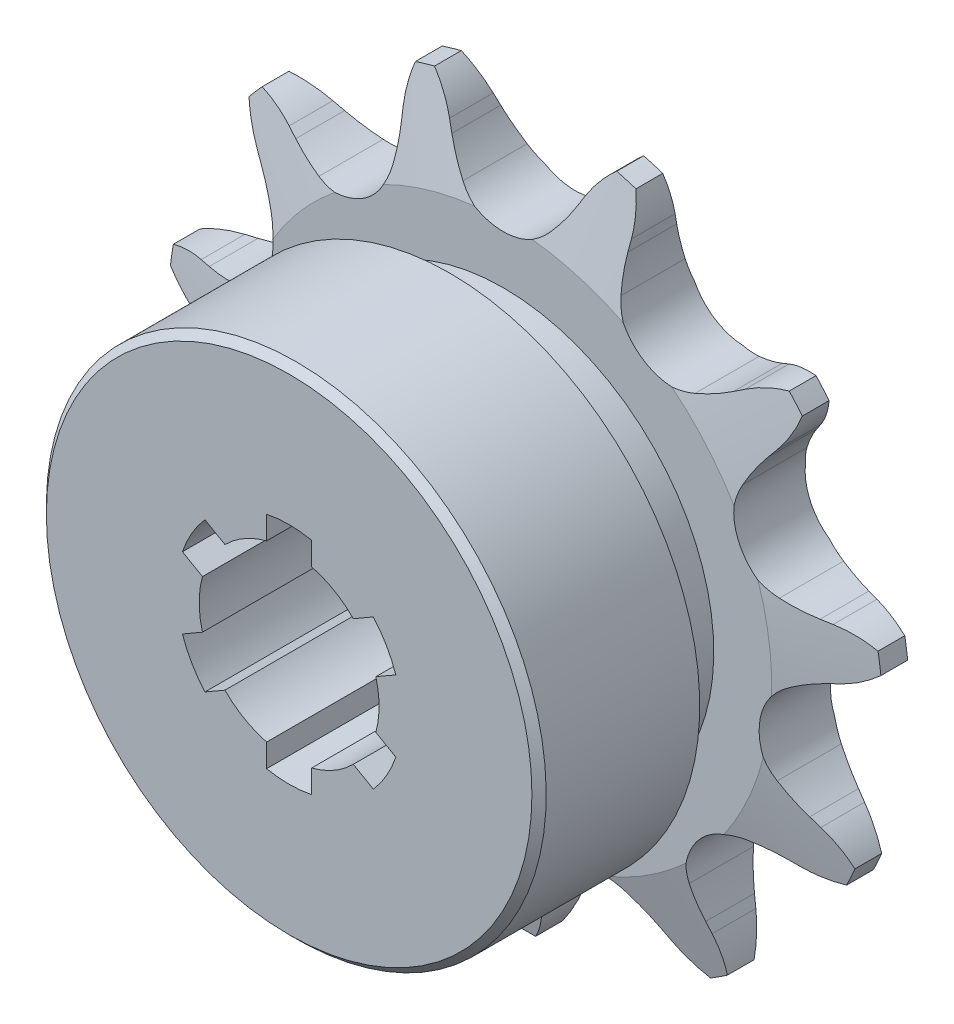
SolidWorks part; units mm, degrees
ref_plane "Front Plane" through (0, 0, 0) normal (0, 0, 1) x (1, 0, 0)
ref_plane "Top Plane" through (0, 0, 0) normal (0, 1, 0) x (1, 0, 0)
ref_plane "Right Plane" through (0, 0, 0) normal (1, 0, 0) x (0, 0, -1)
sketch "Sketch0" plane through (0, 0, 0) normal (0, 0, 1) x (1, 0, 0)
  line L0 (7.9375, -27.0326) -> (0, 0) construction
  line L1 (0, 0) -> (21.2924, -18.45) construction
  line L2 (0, 0) -> (-7.9375, -27.0326) construction
  line L3 (7.9375, -27.0326) -> (21.2924, -18.45) construction
  line L4 (7.9375, -27.0326) -> (-7.9375, -27.0326) construction
  line L5 (13.7041, -25.3103) -> (13.0504, -24.6313)
  line L6 (7.9375, -27.0326) -> (0, -29.3633) construction
  line L7 (2.1552, -28.7014) -> (2.338, -27.7767)
  line L8 (0, -27.0326) -> (0, -31.7951) construction
  line L9 (10.7525, -22.7279) -> (3.4891, -33.8353) construction
  line L10 (0, 0) -> (0, -27.0326) construction
  line L11 (13.0504, -24.6313) -> (3.4891, -33.8353) construction
  line L12 (0, -31.7951) -> (0, -32.9086) construction
  line L13 (19.9035, -19.3426) -> (13.7041, -25.3103) construction
  circle A0 centre (0, 0) radius 31.7951 construction
  circle A1 centre (0, 0) radius 28.1739 construction
  arc A2 (-8.2356, -35.414) -> (26.0745, -25.3397) centre (0, 0) ccw
  circle A3 centre (0, 0) radius 32.9086 construction
  circle A4 centre (7.9375, -27.0326) radius 5.08 construction
  arc A7 (10.7525, -22.7279) -> (3.242, -24.9331) centre (7.9375, -27.0326) ccw
  circle A8 centre (7.9375, -27.0326) radius 5.1435 construction
  arc A9 (13.7041, -25.3103) -> (26.0745, -25.3397) centre (19.9035, -19.3426) ccw
  arc A10 (13.0504, -24.6313) -> (10.7525, -22.7279) centre (3.4891, -33.8353) ccw
  arc A11 (2.1552, -28.7014) -> (-8.2356, -35.414) centre (-6.2865, -27.0326) cw
  arc A12 (2.338, -27.7767) -> (3.242, -24.9331) centre (15.3575, -30.3504) cw
  dimension "D1" = 5.1435
  dimension "R" = 5.1435
sketch "Sketch1" plane through (0, 0, 0) normal (1, 0, 0) x (0, 0, -1)
  line L0 (3.175, 0) -> (-3.175, 0)
  line L1 (-3.175, 0) -> (-3.175, 23.8576)
  line L2 (-3.175, 23.8576) -> (-1.1906, 31.7951)
  line L3 (-1.1906, 31.7951) -> (1.1906, 31.7951)
  line L4 (1.1906, 31.7951) -> (3.175, 23.8576)
  line L5 (3.175, 23.8576) -> (3.175, 0)
  line L7 (0, 31.7951) -> (0, 0) construction
  line L8 (-3.175, 23.8576) -> (3.175, 23.8576) construction
  line L9 (0, 31.7951) -> (0, -31.7951) construction
  line L10 (-3.175, 23.8576) -> (-3.175, 31.7951) construction
  line L11 (-3.175, 31.7951) -> (-1.1906, 31.7951) construction
  line L12 (1.1906, 31.7951) -> (3.175, 31.7951) construction
  line L13 (3.175, 31.7951) -> (3.175, 23.8576) construction
  line L14 (0, 0) -> (-6.4008, 0) construction
  line L22 (3.175, 0) -> (-22.225, 0) construction
  line L24 (-3.175, 0) -> (-3.175, 18.7141) construction
revolve "Revolve1" add sketch "Sketch1" angle 360 mid plane about L0
extrude "Cut-Extrude1" cut sketch "Sketch0" against normal through all and the other way through all
pattern_circular "CirPattern1" count 11 over 360 about axis through (0, 0, -3.175) along (0, 0, -1) of "Cut-Extrude1"
sketch "Sketch2" plane through (0, 0, 0) normal (0, 0, 1) x (1, 0, 0)
  circle A0 centre (0, 0) radius 7.9375 construction
  circle A1 centre (0, 0) radius 22.225
  circle A2 centre (0, 0) radius 31.75 construction
  dimension "Bore" = 15.875
  dimension "Hub Dia." = 44.45
  dimension "OD" = 63.5
extrude "Boss-Extrude1" add sketch "Sketch2" along normal up to vertex (22.225 mm away) from surface up to point (0, 0, 22.225) starting at face at (0, 0, 3.175)
sketch "Sketch3" plane through (0, 0, 0) normal (0, 0, 1) x (1, 0, 0)
  circle A0 centre (0, 0) radius 7.9375 construction
  circle A1 centre (0, 0) radius 7.9375
extrude "Cut-Extrude2" cut sketch "Sketch3" along normal through all and the other way through all
sketch "Sketch4" plane through (0, 0, 0) normal (1, 0, 0) x (0, 0, -1)
  line L0 (-22.225, 22.225) -> (-22.225, 21.59)
  line L1 (-3.175, 31.7951) -> (-7.9375, 31.7951)
  line L2 (-3.175, 31.7951) -> (-3.175, 18.7141)
  line L3 (-3.175, 18.7141) -> (-7.9375, 18.7141)
  line L4 (-7.9375, 31.7951) -> (-7.9375, 18.7141)
  line L9 (-22.225, 21.59) -> (-21.59, 22.225)
  line L10 (-21.59, 22.225) -> (-22.225, 22.225)
  dimension "C" = 0.635
  dimension "D3" = 4.7625
revolve "Cut-Revolve1" cut sketch "Sketch4" angle 360 mid plane about L22
ref_plane "Plane1" through (0, 0, 0) normal (0, 0, -1) x (-1, 0, 0)
ref_axis "Axis1" through (0, 0, 36.6519) along (0, 0, -1)
sketch "Sketch5" plane through (0, 0, -3.175) normal (0, 0, -1) x (-1, 0, 0)
  line L0 (7.6603, -6.7321) -> (9.6603, -3.2679)
  line L1 (2, -10) -> (-2, -10)
  line L2 (2, -10) -> (2, 10)
  line L3 (2, 10) -> (-2, 10)
  line L4 (-2, -10) -> (-2, 10)
  line L5 (2, -10) -> (-2, 10) construction
  line L6 (2, 10) -> (-2, -10) construction
  line L7 (-7.6603, 6.7321) -> (9.6603, -3.2679)
  line L8 (-9.6603, 3.2679) -> (7.6603, -6.7321)
  line L9 (-9.6603, 3.2679) -> (-7.6603, 6.7321)
  line L10 (-9.6603, -3.2679) -> (-7.6603, -6.7321)
  line L11 (9.6603, 3.2679) -> (-7.6603, -6.7321)
  line L12 (7.6603, 6.7321) -> (-9.6603, -3.2679)
  line L13 (7.6603, 6.7321) -> (9.6603, 3.2679)
  circle A0 centre (0, 0) radius 8
  circle A1 centre (0, 0) radius 10
  point P18 (0, 0)
  dimension "D1" = 16
  dimension "D2" = 20
  dimension "D3" = 4
  dimension "D4" = 3
extrude "Cut-Extrude3" cut sketch "Sketch5" against normal through all contours L2 A1 L4 A0 | L11 A1 L12 A0 | L8 A1 L7 A0 | L4 A1 L2 A0 | L12 A1 L11 A0 | L7 A1 L8 A0 | A0 region at (-7.7283, -4.4619, -3.175) region at (0, -8.9239, -3.175) region at (-7.7283, 4.4619, -3.175) region at (7.7283, -4.4619, -3.175) region at (0, 8.9239, -3.175) region at (7.7283, 4.4619, -3.175)
ref_point "Point1"
ref_point "Point2"
ref_point "Point3"
ref_point "Point4"
ref_point "Point5"
ref_point "Point6"
ref_point "Point7"
equation "\"360/N@Sketch0\" = 360/\"Teeth@CirPattern1\""
equation "\"Ds@Sketch0\" = 1.005 * \"Dr@Sketch0\" + 0.003"
equation "\"R@Sketch0\" = 1/2 * \"Ds@Sketch0\""
equation "\"A@Sketch0\" = 35 +  ( 60 / \"Teeth@CirPattern1\" ) "
equation "\"B@Sketch0\" = 18 -  ( 56 / \"Teeth@CirPattern1\" )"
equation "\"ac@Sketch0\" = 0.8 * \"Dr@Sketch0\""
equation "\"ab@Sketch0\" = 1.4 * \"Dr@Sketch0\""
equation "\"J@Sketch0\" = 0.3 * \"Pitch@Sketch0\""
equation "\"h@Sketch1\" = \"Pitch@Sketch0\" / 2"
equation "\"g@Sketch1\" = \"h@Sketch1\" / 4"
equation "\"MHD@Sketch1\" = \"Pitch@Sketch0\" * ( cotan ( 180 / \"Teeth@CirPattern1\" ) - 1 ) - 0.030"
equation "\"D3@Sketch4\" = \"t@Sketch1\" * 3 / 4"
